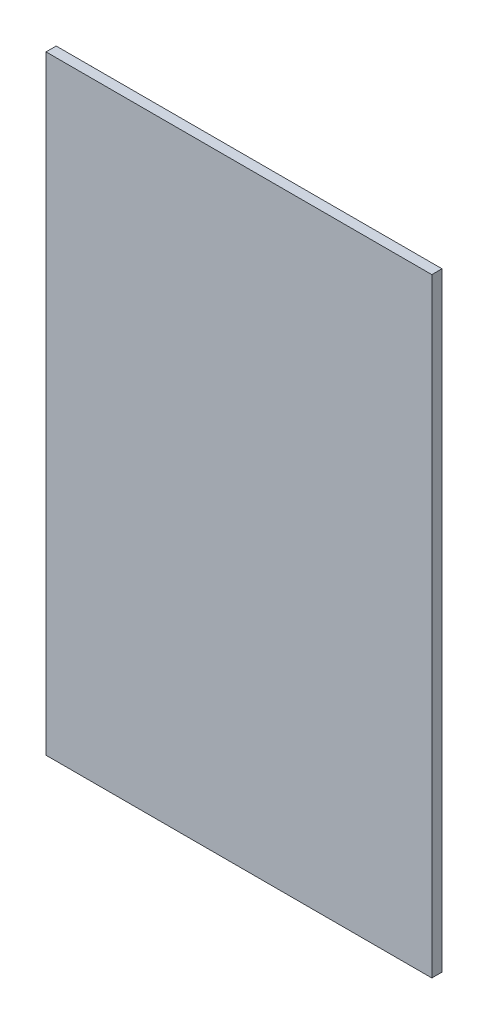
SolidWorks part; units mm, degrees
ref_plane "Plan de face" through (0, 0, 0) normal (0, 0, 1) x (1, 0, 0)
ref_plane "Plan de dessus" through (0, 0, 0) normal (0, 1, 0) x (1, 0, 0)
ref_plane "Plan de droite" through (0, 0, 0) normal (1, 0, 0) x (0, 0, -1)
sketch "Esquisse1" plane through (0, 0, 0) normal (0, 0, 1) x (1, 0, 0)
  line L2 (0, 0) -> (-380, 0)
  line L3 (0, 0) -> (0, 600)
  line L4 (0, 600) -> (-380, 600)
  line L5 (-380, 0) -> (-380, 600)
  dimension "D1" = 380
  dimension "D2" = 600
extrude "Boss.-Extru.1" add sketch "Esquisse1" against normal blind 10
